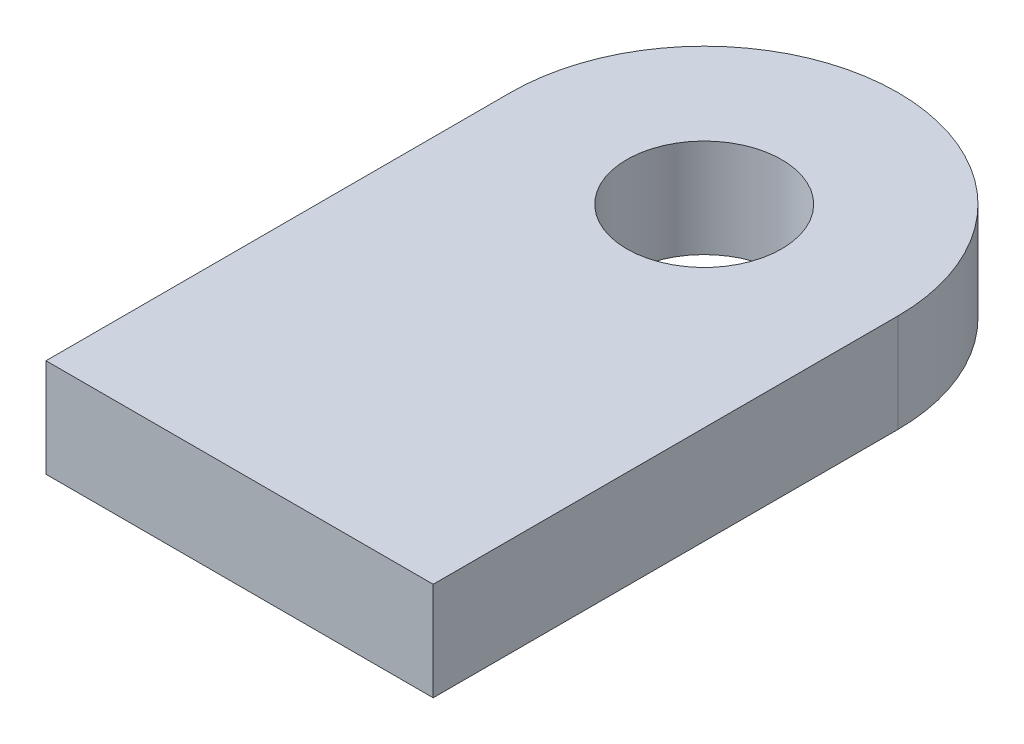
SolidWorks part; units mm, degrees
ref_plane "Front Plane" through (0, 0, 0) normal (0, 0, 1) x (1, 0, 0)
ref_plane "Top Plane" through (0, 0, 0) normal (0, 1, 0) x (1, 0, 0)
ref_plane "Right Plane" through (0, 0, 0) normal (1, 0, 0) x (0, 0, -1)
sketch "Sketch1" plane through (0, 0, 0) normal (0, 1, 0) x (1, 0, 0)
  line L0 (-22.78, 39.7975) -> (-22.78, 9.7975)
  line L1 (2.22, 39.7975) -> (2.22, 9.7975)
  line L2 (-22.78, 9.7975) -> (2.22, 9.7975)
  circle A1 centre (-10.28, 39.7975) radius 12.5
  circle A2 centre (-10.28, 39.7975) radius 5
  dimension "D1" = 10
  dimension "D2" = 25
  dimension "D3" = 30
extrude "Boss-Extrude1" add sketch "Sketch1" along normal blind 6.35 contours A1 L0 L1 | A1 A2 region at (-10.28, 0, -20.0816) region at (-10.28, 0, -51.9439)
